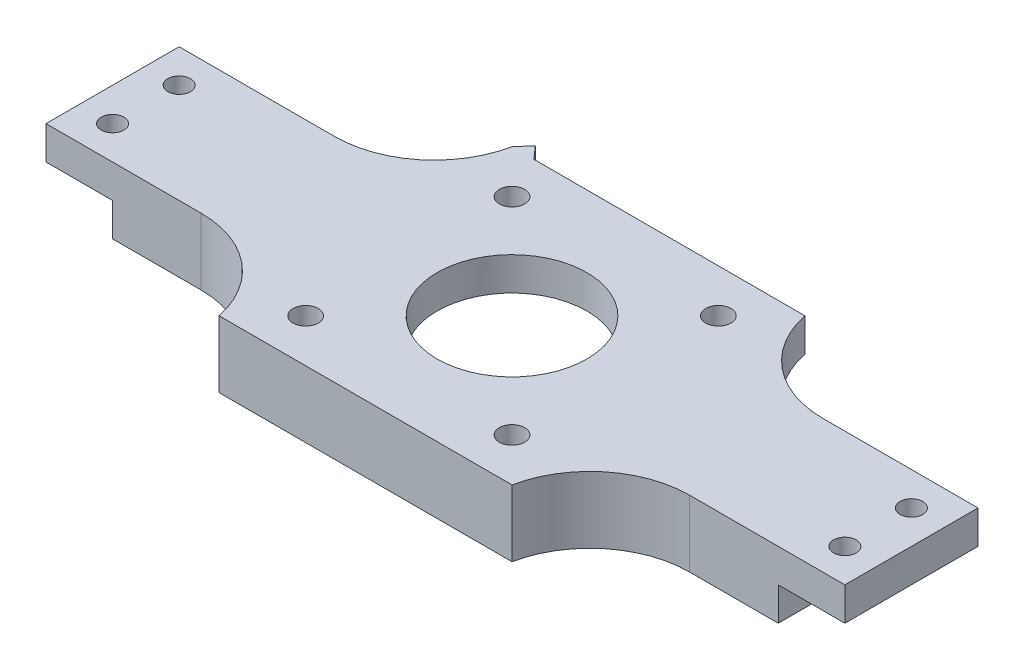
SolidWorks part; units mm, degrees
ref_plane "Ebene vorne" through (0, 0, 0) normal (0, 0, 1) x (1, 0, 0)
ref_plane "Ebene oben" through (0, 0, 0) normal (0, 1, 0) x (1, 0, 0)
ref_plane "Ebene rechts" through (0, 0, 0) normal (1, 0, 0) x (0, 0, -1)
sketch "Skizze1" plane through (0, 0, 0) normal (0, 1, 0) x (1, 0, 0)
  line L0 (-60, -4.8) -> (-22, -4.8)
  line L1 (60, -4.8) -> (60, 15.2)
  line L2 (60, 15.2) -> (22, 15.2)
  line L3 (0, 10.4) -> (0, 0) construction
  line L4 (-60, -4.8) -> (-60, 15.2)
  line L5 (22, -4.8) -> (60, -4.8)
  line L6 (-22, 15.2) -> (-22, 27.2)
  line L7 (-15.5, -10.3) -> (15.5, -10.3) construction
  line L8 (-15.5, -10.3) -> (-15.5, 20.7) construction
  line L9 (-15.5, 20.7) -> (15.5, 20.7) construction
  line L10 (15.5, -10.3) -> (15.5, 20.7) construction
  line L11 (-15.5, -10.3) -> (15.5, 20.7) construction
  line L12 (-15.5, 20.7) -> (15.5, -10.3) construction
  line L13 (-22, -16.8) -> (22, -16.8)
  line L14 (-22, -16.8) -> (-22, -4.8)
  line L15 (-22, 27.2) -> (0, 27.2)
  line L16 (22, -16.8) -> (22, -4.8)
  line L17 (-22, -16.8) -> (22, 27.2) construction
  line L18 (-22, 27.2) -> (22, -16.8) construction
  line L19 (22, 15.2) -> (22, 27.2)
  line L20 (-22, 15.2) -> (-60, 15.2)
  line L21 (0, 5.2) -> (-66.3854, 5.2) construction
  line L22 (0, 5.2) -> (0, 50.559) construction
  line L23 (0, 27.2) -> (22, 27.2)
  point P7 (0, 5.2)
  point P8 (0, 5.2)
  point P11 (-60, 5.2)
  dimension "D3" = 31
  dimension "D1" = 120
  dimension "D2" = 20
  dimension "D4" = 44
  dimension "D5" = 44
extrude "Aufsatz-Linear austragen1" add sketch "Skizze1" along normal blind 10
sketch "Skizze4" plane through (-60, 0, 0) normal (1, 0, 0) x (0, 0, -1)
  line L0 (-4.8, 10) -> (15.2, 10)
  line L1 (15.2, 10) -> (15.2, 9.0736)
  line L2 (15.2, 10) -> (15.2, 0) construction
  line L3 (-4.8, 10) -> (-4.8, 5.2708)
  line L4 (-4.8, 10) -> (-4.8, 0) construction
  arc A1 (-4.8, 5.2708) -> (15.2, 9.0736) centre (58.0172, -270.6068) cw
extrude "Schnitt-Linear austragen2" [suppressed] cut sketch "Skizze4" along normal blind 10
fillet "Verrundung1" [suppressed] radius 10
mirror "Spiegeln1" [suppressed] about plane through (0, 0, 0) normal (1, 0, 0)
sketch "Skizze6" plane through (0, 10, 0) normal (0, 1, 0) x (1, 0, 0)
  line L0 (0, 27.2) -> (0, -16.8) construction
  line L3 (22, 27.2) -> (-22, 27.2) construction
  line L4 (-15.5, -10.3) -> (15.5, -10.3) construction
  line L5 (-15.5, -10.3) -> (-15.5, 20.7) construction
  line L6 (-15.5, 20.7) -> (15.5, 20.7) construction
  line L7 (15.5, -10.3) -> (15.5, 20.7) construction
  line L8 (-15.5, -10.3) -> (15.5, 20.7) construction
  line L9 (-15.5, 20.7) -> (15.5, -10.3) construction
  line L10 (-22, -16.8) -> (22, -16.8) construction
  circle A0 centre (15.5, 20.7) radius 1.9
  circle A1 centre (15.5, -10.3) radius 1.9
  circle A2 centre (-15.5, -10.3) radius 1.9
  circle A3 centre (-15.5, 20.7) radius 1.9
  circle A4 centre (0, 5.2) radius 11.25
  point P6 (0, 5.2)
  dimension "D2" = 3.8
  dimension "D3" = 22.5
  dimension "D1" = 31
extrude "Schnitt-Linear austragen4" cut sketch "Skizze6" against normal through all
sketch "Skizze7" plane through (-22, 0, 0) normal (-1, 0, 0) x (0, 0, 1)
  line L0 (-36.0808, 5) -> (-15.2, 5)
  line L2 (-15.2, 10) -> (-15.2, 0) construction
  line L3 (-15.2, 5) -> (-15.2, 0)
  line L4 (-15.2, 0) -> (-36.0808, 0)
  line L6 (-36.0808, 5) -> (-36.0808, 0)
extrude "Schnitt-Linear austragen5" cut sketch "Skizze7" against normal through all
fillet "Verrundung2" [suppressed] radius 10
fillet "Verrundung3" radius 15 4 edges at (-22, 7.5, -15.2) (-22, 5, 4.8) (22, 5, 4.8) (22, 7.5, -15.2)
fillet "Verrundung4" [suppressed] radius 22
sketch "Skizze8" plane through (0, 0, -15.2) normal (0, 0, -1) x (-1, 0, 0)
  line L6 (-60, 5) -> (-50, 5)
  line L7 (-60, 10) -> (-60, 0) construction
  line L8 (-50, 5) -> (-50, 0)
  line L9 (-60, 0) -> (-5.1539, 0) construction
  line L10 (-50, 0) -> (-60, 0)
  line L11 (-60, 0) -> (-60, 5)
  line L12 (0, 0) -> (0, 15.1362) construction
  line L13 (-11.25, 0) -> (11.25, 0) construction
  line L14 (60, 0) -> (60, 5)
  line L15 (50, 0) -> (60, 0)
  line L16 (50, 5) -> (50, 0)
  line L17 (60, 5) -> (50, 5)
  dimension "D1" = 10
extrude "Schnitt-Linear austragen6" cut sketch "Skizze8" against normal through all and the other way through all
sketch "Skizze9" plane through (0, 5, 0) normal (0, -1, 0) x (1, 0, 0)
  line L0 (-60, -5.2) -> (-50, -5.2) construction
  line L1 (-60, 4.8) -> (-60, -15.2) construction
  line L2 (-50, 4.8) -> (-50, -15.2) construction
  line L3 (-55, -5.2) -> (-55, 4.8) construction
  line L4 (-60, 4.8) -> (-50, 4.8) construction
  line L5 (0, 0) -> (0, -8.3592) construction
  circle A0 centre (-55, -0.2) radius 1.7
  circle A1 centre (-55, -10.2) radius 1.7
  circle A2 centre (55, -10.2) radius 1.7
  circle A3 centre (55, -0.2) radius 1.7
  dimension "D1" = 3.4
extrude "Schnitt-Linear austragen7" cut sketch "Skizze9" against normal blind 10
sketch "Skizze10" plane through (0, 10, 0) normal (0, 1, 0) x (1, 0, 0)
  line L0 (-22, 27.2) -> (-20.3604, 29.0682)
  line L1 (-20.3604, 29.0682) -> (-20.3604, 27.2) construction
  line L2 (22, 27.2) -> (-22, 27.2) construction
  line L3 (-18.7207, 27.2) -> (-20.3604, 29.0682)
  line L4 (-18.7207, 27.2) -> (-22, 27.2)
extrude "Aufsatz-Linear austragen2" add sketch "Skizze10" against normal blind 5
sketch "Skizze11" plane through (0, 10, 0) normal (0, 1, 0) x (1, 0, 0)
  line L0 (23.7415, 47.7995) -> (24.8232, 40.4162) construction
  line L1 (24.8232, 40.4162) -> (25.9159, 32.9579) construction
  line L2 (25.9159, 32.9579) -> (25.9159, 14.8182) construction
  line L3 (25.9159, 29.3005) -> (27.5941, 27.3005)
  line L4 (25.9159, 29.3005) -> (24.2377, 27.3005)
  line L5 (24.2377, 27.3005) -> (22, 27.2)
  line L6 (27.5941, 27.3005) -> (28.9419, 17.3602)
  line L7 (28.9419, 17.3602) -> (24.0809, 17.5461)
  line L8 (24.0809, 17.5461) -> (21.4223, 25.8471)
  line L9 (21.4223, 25.8471) -> (22, 27.2)
  arc A0 (-127.1113, 338.6796) -> (126.7578, 338.6796) centre (-0.1768, 211.0567) ccw construction
  arc A1 (22, 27.2) -> (36.6969, 15.2) centre (36.6969, 30.2) ccw construction
  dimension "D1" = 2
  dimension "D2" = 40
extrude "Aufsatz-Linear austragen3" [suppressed] add sketch "Skizze11" against normal up to vertex
fillet "Verrundung5" [suppressed] radius 3
chamfer "Fase1" distance 28 angle 35 2 edges at (-5.1539, 2.5, -15.2) (5.1539, 2.5, -15.2) first distance on face at (-37.9627, 5, -15.2) first distance on face at (37.9627, 5, -15.2)
fillet "Verrundung6" radius 10 4 edges at (-33.1539, 2.5, -15.2) (33.1539, 2.5, -15.2) (-8.7186, 2.5, 1.9098) (8.7186, 2.5, 1.9098)
